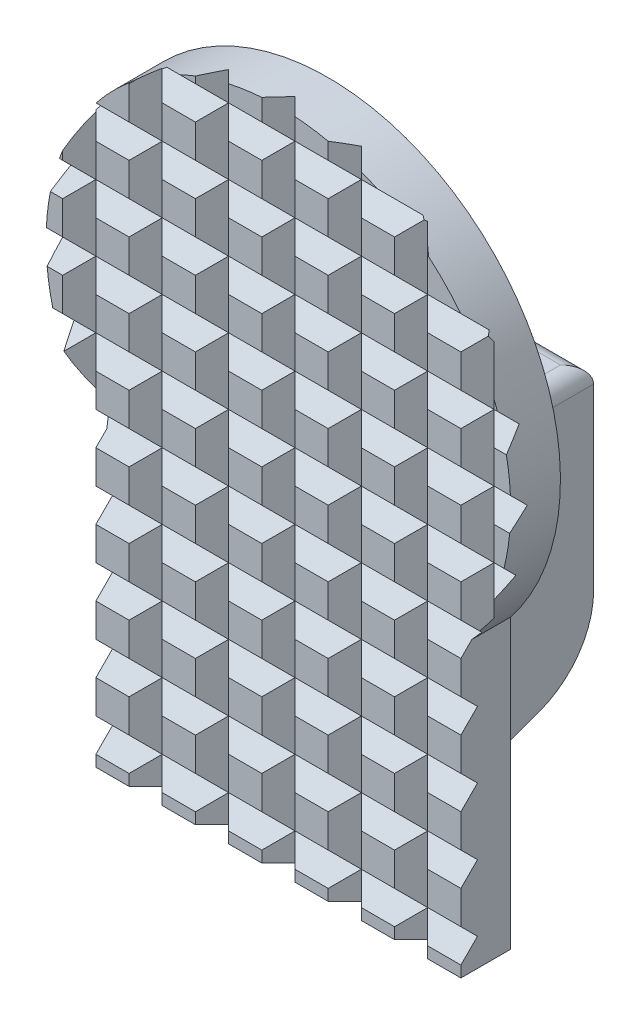
SolidWorks part; units mm, degrees
ref_plane "Спереди" through (0, 0, 0) normal (0, 0, 1) x (1, 0, 0)
ref_plane "Сверху" through (0, 0, 0) normal (0, 1, 0) x (1, 0, 0)
ref_plane "Справа" through (0, 0, 0) normal (1, 0, 0) x (0, 0, -1)
sketch "Эскиз1" plane through (0, 0, 0) normal (0, 0, 1) x (1, 0, 0)
  line L0 (-11, -8.6603) -> (-11, -26)
  line L1 (0, 0) -> (0, -73.1078) construction
  line L2 (-11, -26) -> (11, -26)
  line L3 (11, -8.6603) -> (11, -26)
  arc A0 (11, -8.6603) -> (-11, -8.6603) centre (0, 0) ccw
  point P8 (0, -26)
  dimension "D1" = 28
  dimension "D3" = 40
  dimension "D2" = 22
extrude "Бобышка-Вытянуть1" add sketch "Эскиз1" along normal blind 3
sketch "Эскиз2" plane through (0, 0, 0) normal (1, 0, 0) x (0, 0, -1)
  line L0 (0, -26) -> (9.7101, -22.4658)
  line L1 (13, -17.7673) -> (13, -6)
  line L2 (13, -6) -> (10, -6)
  line L3 (10, -6) -> (9.5, -13.0074)
  line L4 (6.2228, -17.35) -> (0, -19.6149)
  line L5 (0, -26) -> (0, -8.6603) construction
  line L6 (0, -19.6149) -> (0, -26)
  line L7 (-3, -26) -> (0, -26) construction
  arc A0 (9.7101, -22.4658) -> (13, -17.7673) centre (8, -17.7673) ccw
  arc A1 (9.5, -13.0074) -> (6.2228, -17.35) centre (4.5127, -12.6516) cw
  dimension "D4" = 5
  dimension "D5" = 5
  dimension "D1" = 3.5
  dimension "D2" = 6
  dimension "D3" = 13
  dimension "D6" = 3
  dimension "D7" = 20
  dimension "D8" = 20
extrude "Бобышка-Вытянуть2" add sketch "Эскиз2" along normal blind 3 and the other way blind 3
fillet "Скругление1" radius 1 4 edges at (-3, -6, -11.5) (3, -6, -11.5) (0, -6, -13) (0, -6, -10)
fillet "Скругление2" radius 2 3 edges at (0, -19.6149, 0)
sketch "Эскиз3" plane through (0, 0, 0) normal (0, 1, 0) x (1, 0, 0)
  line L0 (0, 0) -> (0, -2) construction
  line L1 (0, -2) -> (-1.1682, -3.1682)
  line L2 (0, -2) -> (0, -3.1682) construction
  line L3 (-1.1682, -3.1682) -> (1.1682, -3.1682)
  line L4 (0, -2) -> (1.1682, -3.1682)
  line L5 (-14, -3) -> (14, -3) construction
  line L6 (2.8318, -3.1682) -> (5.1682, -3.1682)
  line L7 (4, -2) -> (2.8318, -3.1682)
  line L8 (4, -2) -> (5.1682, -3.1682)
  line L9 (6.8318, -3.1682) -> (9.1682, -3.1682)
  line L10 (8, -2) -> (6.8318, -3.1682)
  line L11 (8, -2) -> (9.1682, -3.1682)
  line L12 (10.8318, -3.1682) -> (13.1682, -3.1682)
  line L13 (12, -2) -> (10.8318, -3.1682)
  line L14 (12, -2) -> (13.1682, -3.1682)
  line L15 (-5.1682, -3.1682) -> (-2.8318, -3.1682)
  line L16 (-4, -2) -> (-2.8318, -3.1682)
  line L17 (-9.1682, -3.1682) -> (-6.8318, -3.1682)
  line L18 (-8, -2) -> (-6.8318, -3.1682)
  line L19 (-13.1682, -3.1682) -> (-10.8318, -3.1682)
  line L20 (-12, -2) -> (-10.8318, -3.1682)
  line L21 (-4, -2) -> (-5.1682, -3.1682)
  line L22 (-8, -2) -> (-9.1682, -3.1682)
  line L23 (-12, -2) -> (-13.1682, -3.1682)
  dimension "D1" = 90
  dimension "D2" = 1
  dimension "D3" = 4
  dimension "D4" = 4
  dimension "D5" = 4
extrude "Вырез-Вытянуть1" cut sketch "Эскиз3" against normal through all and the other way through all
sketch "Эскиз4" plane through (0, 0, 0) normal (1, 0, 0) x (0, 0, -1)
  line L0 (-2, -24.3228) -> (-8.6405, -24.3228) construction
  line L1 (-2, -24.3228) -> (-3.3262, -22.9966)
  line L2 (-2, -24.3228) -> (-3.3262, -25.649)
  line L3 (-3.3262, -25.649) -> (-3.3262, -22.9966)
  line L4 (-3, -8.6603) -> (-3, -26) construction
  line L5 (-3.3262, -21.649) -> (-3.3262, -18.9966)
  line L6 (-2, -20.3228) -> (-3.3262, -18.9966)
  line L7 (-2, -20.3228) -> (-3.3262, -21.649)
  line L8 (-3.3262, -17.649) -> (-3.3262, -14.9966)
  line L9 (-2, -16.3228) -> (-3.3262, -14.9966)
  line L10 (-2, -16.3228) -> (-3.3262, -17.649)
  line L11 (-3.3262, -13.649) -> (-3.3262, -10.9966)
  line L12 (-2, -12.3228) -> (-3.3262, -10.9966)
  line L13 (-2, -12.3228) -> (-3.3262, -13.649)
  line L14 (-3.3262, -9.649) -> (-3.3262, -6.9966)
  line L15 (-2, -8.3228) -> (-3.3262, -6.9966)
  line L16 (-2, -8.3228) -> (-3.3262, -9.649)
  line L17 (-3.3262, -5.649) -> (-3.3262, -2.9966)
  line L18 (-2, -4.3228) -> (-3.3262, -2.9966)
  line L19 (-2, -4.3228) -> (-3.3262, -5.649)
  line L20 (-3.3262, -1.649) -> (-3.3262, 1.0034)
  line L21 (-2, -0.3228) -> (-3.3262, 1.0034)
  line L22 (-2, -0.3228) -> (-3.3262, -1.649)
  line L23 (-3.3262, 2.351) -> (-3.3262, 5.0034)
  line L24 (-2, 3.6772) -> (-3.3262, 5.0034)
  line L25 (-2, 3.6772) -> (-3.3262, 2.351)
  line L26 (-3.3262, 6.351) -> (-3.3262, 9.0034)
  line L27 (-2, 7.6772) -> (-3.3262, 9.0034)
  line L28 (-2, 7.6772) -> (-3.3262, 6.351)
  line L29 (-3.3262, 10.351) -> (-3.3262, 13.0034)
  line L30 (-2, 11.6772) -> (-3.3262, 13.0034)
  line L31 (-2, 11.6772) -> (-3.3262, 10.351)
  dimension "D1" = 90
  dimension "D2" = 45
  dimension "D3" = 1
  dimension "D4" = 10
extrude "Вырез-Вытянуть2" cut sketch "Эскиз4" against normal through all and the other way through all
